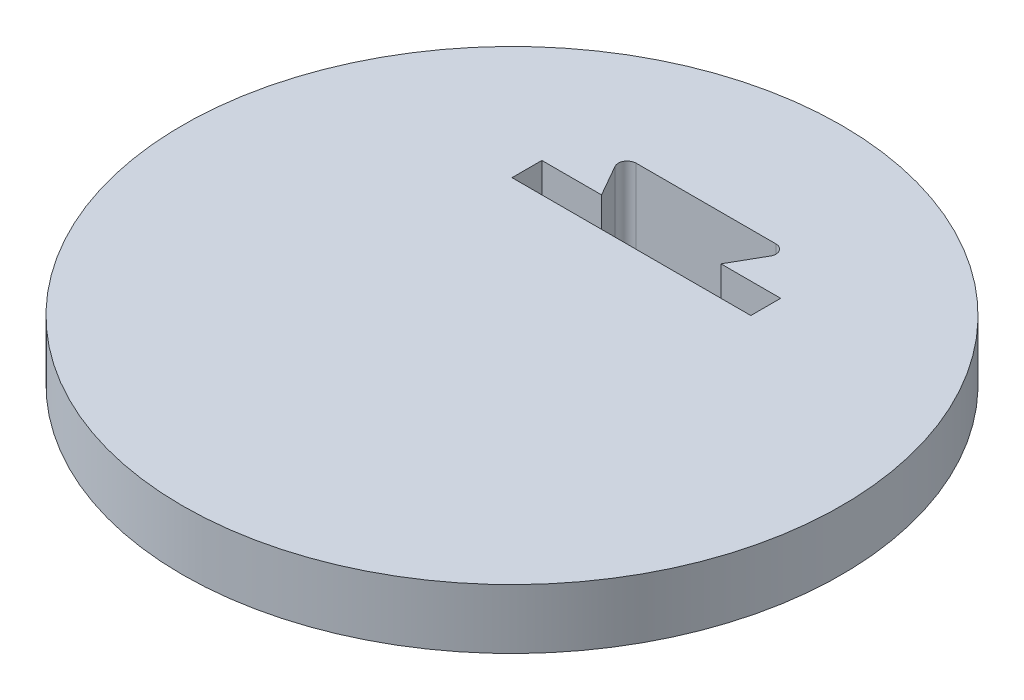
SolidWorks part; units mm, degrees
ref_plane "Front Plane" through (0, 0, 0) normal (0, 0, 1) x (1, 0, 0)
ref_plane "Top Plane" through (0, 0, 0) normal (0, 1, 0) x (1, 0, 0)
ref_plane "Right Plane" through (0, 0, 0) normal (1, 0, 0) x (0, 0, -1)
sketch "Sketch1" plane through (0, 0, 0) normal (0, 1, 0) x (1, 0, 0)
  circle A0 centre (0, 0) radius 17.526
  dimension "D1" = 35.052
extrude "Boss-Extrude1" add sketch "Sketch1" against normal blind 3.175
sketch "Sketch2" plane through (0, 0, 0) normal (0, 0, 1) x (1, 0, 0)
  line L0 (-17.526, -3.175) -> (0, -3.175)
  line L1 (0, 7.3946) -> (0, -9.4405) construction
  line L2 (0, -4.7625) -> (0, -3.175)
  arc A0 (-17.526, -3.175) -> (0, -4.7625) centre (-0.7827, 84.1341) ccw
  point P2 (0, -4.9538)
  dimension "D1" = 88.9
  dimension "D2" = 1.5875
revolve "Revolve2" add sketch "Sketch2" angle 360 about L1
sketch "Sketch4" plane through (0, 0, 0) normal (0, 1, 0) x (1, 0, 0)
  line L0 (-3.175, 7.9375) -> (-4.1287, 9.607)
  line L1 (-6.35, 7.9375) -> (-3.175, 7.9375)
  line L2 (-6.35, 7.9375) -> (-6.35, 6.35)
  line L3 (-6.35, 6.35) -> (6.35, 6.35)
  line L4 (6.35, 7.9375) -> (6.35, 6.35)
  line L5 (-3.7156, 10.3187) -> (3.7156, 10.3188)
  line L6 (4.1287, 9.607) -> (3.175, 7.9375)
  line L8 (3.175, 7.9375) -> (6.35, 7.9375)
  line L9 (0, 6.35) -> (0, -3.5631) construction
  line L10 (-3.175, 7.9375) -> (3.175, 7.9375)
  arc A0 (-4.1287, 9.607) -> (-3.7156, 10.3187) centre (-3.7156, 9.843) cw
  arc A1 (4.1287, 9.607) -> (3.7156, 10.3188) centre (3.7156, 9.843) ccw
  dimension "D1" = 12.7
  dimension "D2" = 1.5875
  dimension "D3" = 2.3813
  dimension "D4" = 6.35
  dimension "D5" = 3.175
  dimension "D6" = 6.35
extrude "Cut-Extrude2" cut sketch "Sketch4" against normal blind 4.572 contours L6 A1 L5 A0 L0 L10 region at (0, 0, -9.1821)
extrude "Cut-Extrude3" cut sketch "Sketch4<4>" against normal blind 4.064 contours L10 L1 L2 L3 L4 L8 region at (0, 0, -7.1438)
sketch "Sketch4<4>" plane through (0, 0, 0) normal (0, 1, 0) x (1, 0, 0) same geometry as "Sketch4"
